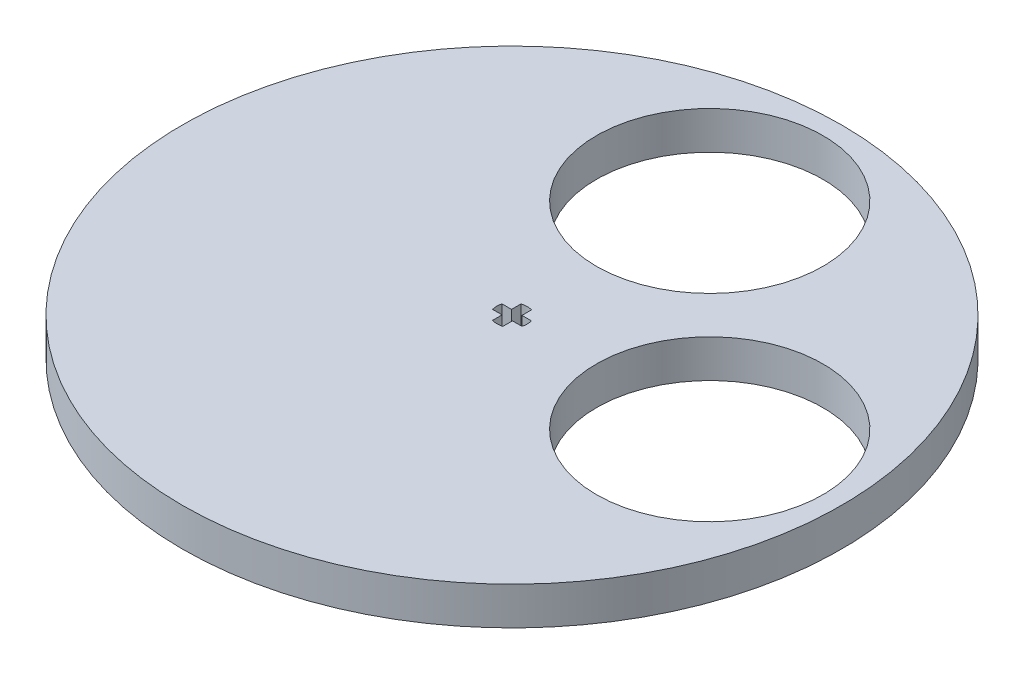
SolidWorks part; units mm, degrees
ref_plane "Front Plane" through (0, 0, 0) normal (0, 0, 1) x (1, 0, 0)
ref_plane "Top Plane" through (0, 0, 0) normal (0, 1, 0) x (1, 0, 0)
ref_plane "Right Plane" through (0, 0, 0) normal (1, 0, 0) x (0, 0, -1)
sketch "Sketch6" plane through (0, 0, 0) normal (0, 1, 0) x (1, 0, 0)
  circle A2 centre (63.5, 63.5) radius 50.8
  dimension "D1" = 101.6
extrude "Boss-Extrude3" add sketch "Sketch6" along normal blind 5.842 contours A2
sketch "Sketch11" plane through (0, 5.842, 0) normal (0, 1, 0) x (1, 0, 0)
  line L0 (63.5, 114.3) -> (63.5, 63.5)
  line L1 (63.5, 63.5) -> (114.3, 63.5)
  line L2 (63.5, 63.5) -> (63.5, 12.7) construction
  line L3 (63.5, 63.5) -> (12.7, 63.5) construction
  circle A0 centre (63.5, 93.98) radius 17.4625
  circle A1 centre (93.98, 63.5) radius 17.4625
  circle A2 centre (63.5, 63.5) radius 50.8 construction
  circle A3 centre (63.5, 63.5) radius 50.8 construction
  dimension "D1" = 34.925
  dimension "D2" = 20.32
  dimension "D3" = 20.32
extrude "Cut-Extrude2" cut sketch "Sketch11" against normal through all contours L0 A0 | L0 A0 | L1 A1 | L1 A1 | A0 region at (70.9113, 5.842, -93.98) region at (93.98, 5.842, -70.9113) region at (93.98, 5.842, -56.0887) region at (56.0887, 5.842, -93.98)
sketch "Sketch12" plane through (0, 5.842, 0) normal (0, 1, 0) x (1, 0, 0)
  line L0 (62.7, 64.2314) -> (62.7, 65.6941)
  line L1 (64.3, 65.6941) -> (64.3, 64.2314)
  line L2 (62.7, 64.2314) -> (64.3, 64.2314) construction
  line L3 (62.7, 64.2314) -> (62.7, 62.7686) construction
  line L4 (62.7, 64.2314) -> (61.2373, 64.2314)
  line L5 (61.2373, 62.7686) -> (62.7, 62.7686)
  line L6 (62.7, 62.7686) -> (62.7, 61.3059)
  line L7 (64.3, 61.3059) -> (64.3, 62.7686)
  line L8 (64.3, 62.7686) -> (65.7627, 62.7686)
  line L9 (64.3, 64.2314) -> (65.7627, 64.2314)
  circle A0 centre (63.5, 63.5) radius 2.75
  circle A1 centre (63.5, 63.5) radius 2.5157 construction
  arc A2 (62.7, 65.6941) -> (64.3, 65.6941) centre (63.5, 63.2202) cw
  arc A3 (61.2373, 64.2314) -> (61.2373, 62.7686) centre (63.7323, 63.5) ccw
  arc A4 (62.7, 61.3059) -> (64.3, 61.3059) centre (63.5, 63.7798) ccw
  arc A5 (65.7627, 64.2314) -> (65.7627, 62.7686) centre (63.2677, 63.5) cw
  point P9 (63.5, 64.2314)
  point P23 (61.1323, 63.5)
  point P24 (63.5, 61.1798)
  dimension "D1" = 5.5
  dimension "D4" = 2.6
  dimension "D5" = 5.0313
  dimension "D2" = 1.4627
  dimension "D3" = 1.6
extrude "Cut-Extrude3" cut sketch "Sketch12" against normal through all contours A0
extrude "Boss-Extrude4" add sketch "Sketch12<3>" against normal up to surface (5.842 mm away) up to face at (63.5, 0, -60.75)
sketch "Sketch12<3>" plane through (0, 5.842, 0) normal (0, 1, 0) x (1, 0, 0) same geometry as "Sketch12"
sketch "Sketch13" plane through (0, 5.842, 0) normal (0, 1, 0) x (1, 0, 0)
  circle A0 centre (63.5, 63.5) radius 2.293
